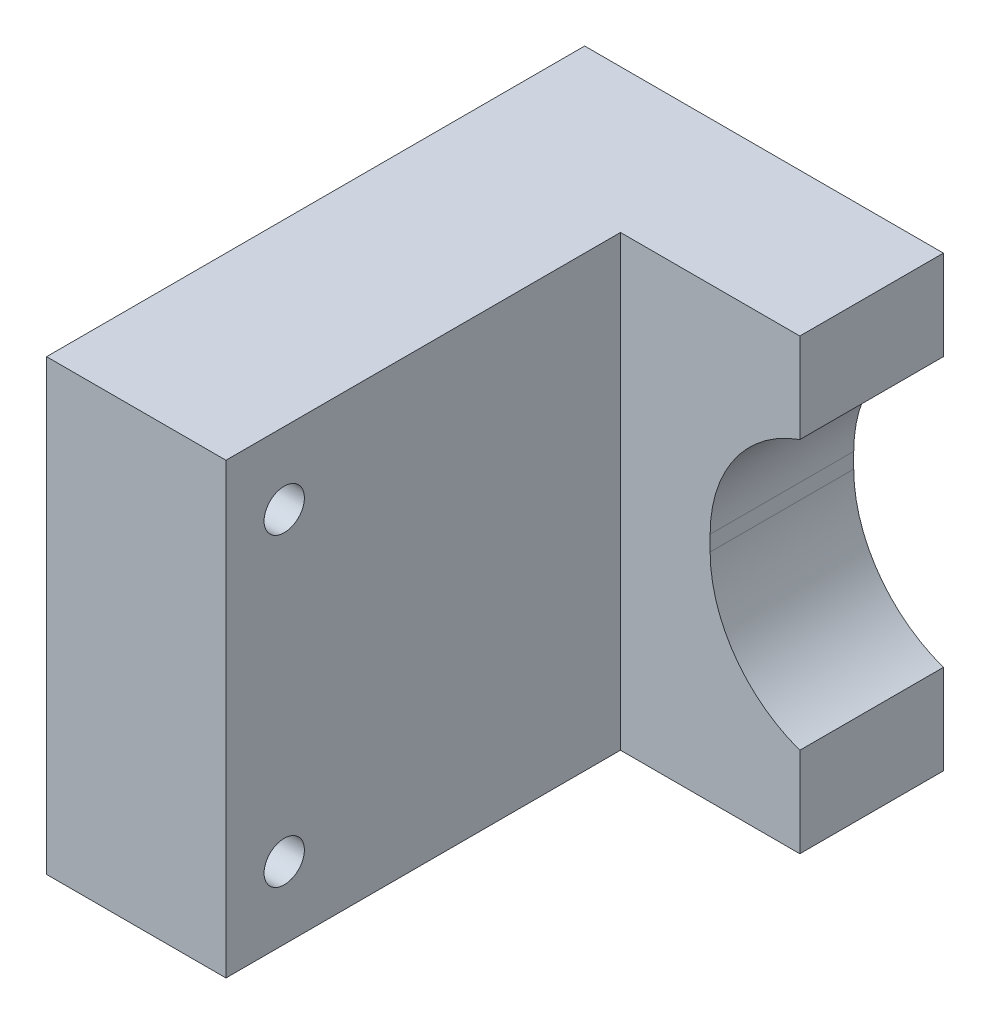
SolidWorks part; units mm, degrees
ref_plane "Front Plane" through (0, 0, 0) normal (0, 0, 1) x (1, 0, 0)
ref_plane "Top Plane" through (0, 0, 0) normal (0, 1, 0) x (1, 0, 0)
ref_plane "Right Plane" through (0, 0, 0) normal (1, 0, 0) x (0, 0, -1)
sketch "Sketch3" plane through (0, 0, 0) normal (0, 1, 0) x (1, 0, 0)
  line L1 (10, -30) -> (-10, -30)
  line L2 (10, -30) -> (10, 30)
  line L3 (10, 30) -> (-10, 30)
  line L4 (-10, -30) -> (-10, 30)
  line L5 (10, -30) -> (-10, 30) construction
  line L6 (10, 30) -> (-10, -30) construction
  line L7 (10, 30) -> (30, 30)
  line L8 (10, 30) -> (10, 13.9904)
  line L9 (10, 13.9904) -> (30, 13.9904)
  line L10 (30, 30) -> (30, 13.9904)
  point P0 (0, 0)
  dimension "D1" = 60
  dimension "D2" = 20
  dimension "D3" = 20
extrude "Boss-Extrude1" add sketch "Sketch3" along normal blind 50 contours L4 L1 L2 L3 | L10 L7 L2 L9 region at (0, 0, 0) region at (20, 0, -21.9952)
sketch "Sketch4" plane through (30, 0, 0) normal (1, 0, 0) x (0, 0, -1)
  line L0 (13.9904, 50) -> (13.9904, 0) construction
  line L1 (13.9904, 40) -> (30, 40)
  line L2 (13.9904, 40) -> (13.9904, 10)
  line L3 (13.9904, 10) -> (30, 10)
  line L4 (30, 40) -> (30, 10)
  line L5 (30, 50) -> (30, 0) construction
  dimension "D1" = 30
  dimension "D2" = 10
extrude "Cut-Extrude1" cut sketch "Sketch4" against normal blind 10
fillet "Fillet4" radius 15 2 edges at (20, 10, -21.9952) (20, 40, -21.9952)
hole_wizard "CSK for #8 Flat Head Machine Screw (100)1" positions "Sketch5" profile "Sketch6" countersink size "#8" standard "ANSI Inch" end condition up to next
sketch "Sketch5" plane through (-10, 0, 0) normal (-1, 0, 0) x (0, 0, 1)
  line L0 (30, 0) -> (-30, 0) construction
  line L1 (30, 50) -> (30, 0) construction
  line L2 (30, 50) -> (-30, 50) construction
  point P0 (23.5, 8)
  point P2 (23.5, 42)
  dimension "D1" = 8
  dimension "D2" = 6.5
  dimension "D3" = 6.5
  dimension "D4" = 8
sketch "Sketch6" plane through (-10, 8, 23.5) normal (0, 1, 0) x (0, 0, 1)
  line L0 (0, 0) -> (0, 20)
  line L1 (0, 20) -> (2.2479, 20)
  line L2 (2.2479, 20) -> (2.2479, 1.6518)
  line L3 (2.2479, 1.6518) -> (4.2164, 0)
  line L5 (4.2164, 0) -> (0, 0)
  line L6 (-2.2479, 1.6518) -> (-4.2164, 0) construction
  line L11 (0, -6.35) -> (0, 107.95) construction
  dimension "Thru Hole Dia." = 4.4958
  dimension "Thru Hole Depth" = 20
  dimension "Near C'Sink Dia." = 8.4328
  dimension "Near C'Sink Angle" = 100
sketch "Sketch7" plane through (0, 0, -30) normal (0, 0, -1) x (-1, 0, 0)
  line L0 (10, 50) -> (10, 0) construction
  line L1 (-30, 50) -> (10, 50) construction
  line L2 (-30, 0) -> (10, 0) construction
  circle A0 centre (0, 10) radius 2.5
  circle A1 centre (0, 40) radius 2.5
  dimension "D1" = 5
  dimension "D2" = 5
  dimension "D3" = 10
  dimension "D4" = 10
  dimension "D5" = 10
  dimension "D6" = 10
extrude "Cut-Extrude2" cut sketch "Sketch7" against normal blind 30
